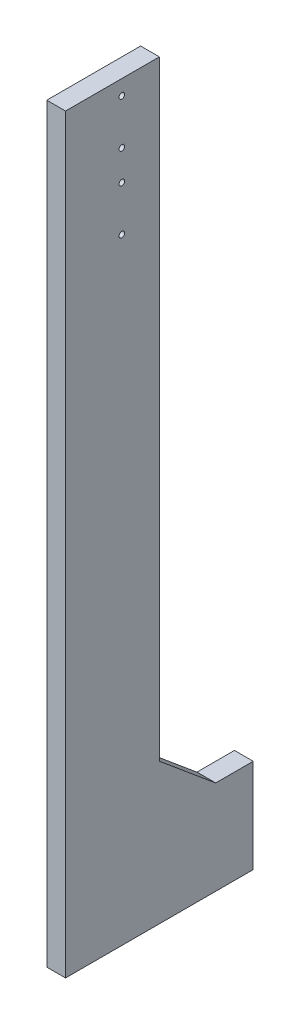
SolidWorks part; units mm, degrees
ref_plane "Спереди" through (0, 0, 0) normal (0, 0, 1) x (1, 0, 0)
ref_plane "Сверху" through (0, 0, 0) normal (0, 1, 0) x (1, 0, 0)
ref_plane "Справа" through (0, 0, 0) normal (1, 0, 0) x (0, 0, -1)
sketch "Эскиз1" plane through (0, 0, 0) normal (1, 0, 0) x (0, 0, -1)
  line L0 (0, 0) -> (100, 0)
  line L1 (100, 0) -> (100, 50)
  line L2 (100, 50) -> (80, 50)
  line L3 (80, 50) -> (50, 75)
  line L4 (50, 75) -> (50, 400)
  line L5 (50, 400) -> (0, 400)
  line L6 (0, 400) -> (0, 0)
  line L7 (30, 308.744) -> (30, 198.3922) construction
  line L8 (61.2557, 380) -> (8.0298, 380) construction
  line L9 (61.2557, 340) -> (8.0298, 340) construction
  circle A0 centre (30, 392) radius 1.5
  circle A1 centre (30, 368) radius 1.5
  circle A2 centre (30, 352) radius 1.5
  circle A3 centre (30, 328) radius 1.5
  point P12 (34.6427, 380)
  point P13 (30, 392)
  dimension "D10" = 40
  dimension "D11" = 3
  dimension "D12" = 3
  dimension "D13" = 3
  dimension "D1" = 100
  dimension "D2" = 50
  dimension "D3" = 50
  dimension "D4" = 400
  dimension "D5" = 20
  dimension "D6" = 25
  dimension "D7" = 20
  dimension "D8" = 20
  dimension "D9" = 12
  dimension "D14" = 12
extrude "Боковая панель" add sketch "Эскиз1" along normal blind 10
